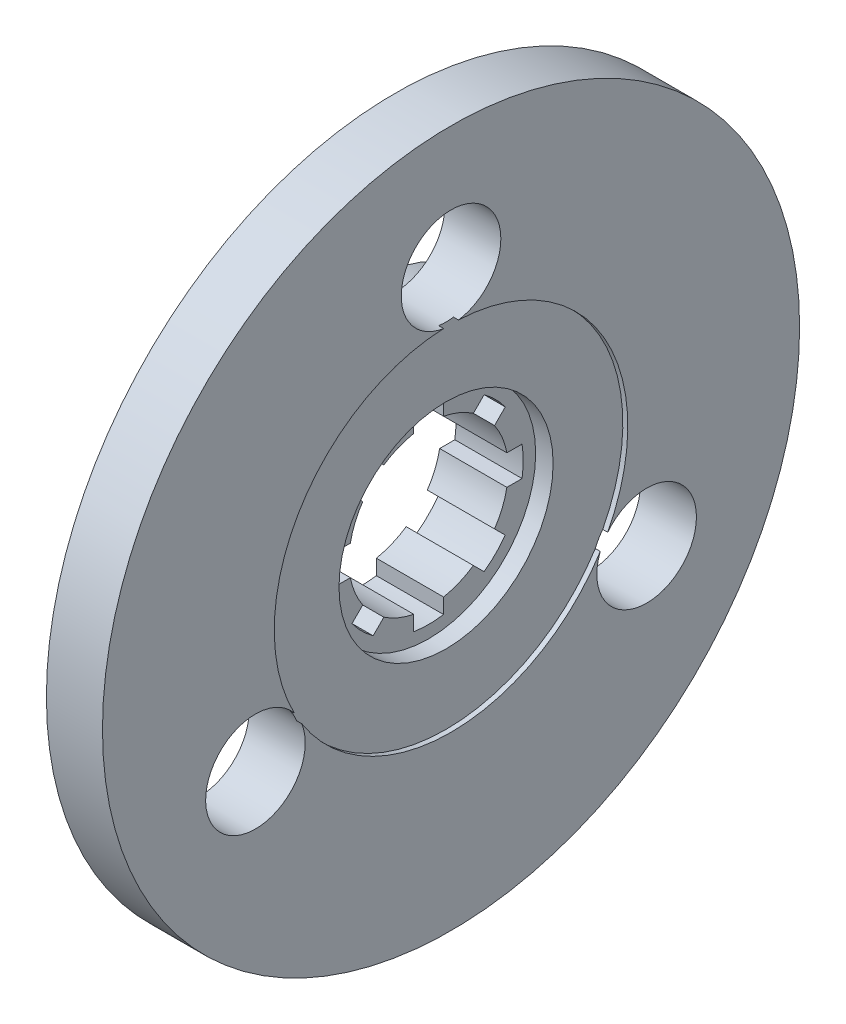
SolidWorks part; units mm, degrees
ref_plane "前视基准面" through (0, 0, 0) normal (0, 0, 1) x (1, 0, 0)
ref_plane "上视基准面" through (0, 0, 0) normal (0, 1, 0) x (1, 0, 0)
ref_plane "右视基准面" through (0, 0, 0) normal (1, 0, 0) x (0, 0, -1)
sketch "草图1" plane through (0, 0, 0) normal (0, 0, 1) x (1, 0, 0)
  line L0 (-66.0175, 0) -> (81.3348, 0) construction
  line L1 (-3.5974, 35.5) -> (-3.5974, 70)
  line L2 (-3.5974, 70) -> (-14.8578, 70)
  line L3 (-14.8578, 70) -> (-14.8578, 33.5)
  line L4 (-14.8578, 33.5) -> (-21.5974, 33.5)
  line L5 (-21.5974, 33.5) -> (-21.5974, 16)
  line L6 (-21.5974, 16) -> (-8.0974, 16)
  line L7 (-8.0974, 16) -> (-8.0974, 21.5)
  line L8 (-8.0974, 21.5) -> (-4.5974, 21.5)
  line L9 (-4.5974, 21.5) -> (-4.5974, 35.5)
  line L10 (-4.5974, 35.5) -> (-3.5974, 35.5)
  point P3 (-4.0974, 35.5)
  dimension "RBig" = 70
  dimension "R3" = 35.5
  dimension "R2" = 21.5
  dimension "R1" = 16
  dimension "B1" = 18
  dimension "B3" = 13.5
  dimension "B4" = 3.5
  dimension "R5" = 33.5
revolve "旋转1" add sketch "草图1" angle 360 about L0
sketch "草图2" plane through (0, 0, 0) normal (1, 0, 0) x (0, 0, -1)
  line L0 (0, -74.586) -> (0, 70) construction
  line L1 (-76.3984, 0) -> (75.0628, 0) construction
  circle A0 centre (0, 0) radius 45.357 construction
  circle A1 centre (0, 0) radius 70 construction
  circle A2 centre (0, 45.357) radius 10
  dimension "RCenter" = 90.714
  dimension "Rhole" = 20
extrude "切除-拉伸1" cut sketch "草图2" against normal through all
pattern_circular "阵列(圆周)1" count 3 over 360 about axis through (-66.0175, 0, 0) along (-1, 0, 0) of "切除-拉伸1"
sketch "草图3" plane through (0, 0, 0) normal (1, 0, 0) x (0, 0, -1)
  line L1 (3, 15.7162) -> (3, 18.7617)
  line L2 (-3, 15.7162) -> (-3, 18.7617)
  arc A0 (3, 18.7617) -> (-3, 18.7617) centre (0, 0) ccw
  circle A1 centre (0, 0) radius 16 construction
  arc A2 (3, 15.7162) -> (-3, 15.7162) centre (0, 0) ccw
  dimension "RKEY" = 19
  dimension "Bkey" = 6
extrude "切除-拉伸2" cut sketch "草图3" against normal through all
pattern_circular "阵列(圆周)2" count 8 over 360 about axis through (-66.0175, 0, 0) along (-1, 0, 0) of "切除-拉伸2"
ref_plane "基准面1" through (-8.0974, 0, 0) normal (1, 0, 0) x (0, 0, -1)
ref_plane "基准面2" through (-14.8578, 0, 0) normal (-1, 0, 0) x (0, 0, 1)
ref_plane "addMate3" through (0, 0, 0) normal (0, 0.9239, -0.3827) x (1, 0, 0)
ref_axis "基准轴1" through (-14.8578, -22.6785, 39.2803) along (1, 0, 0)
ref_plane "基准面3" through (-3.5974, 0, 0) normal (1, 0, 0) x (0, 0, -1)
